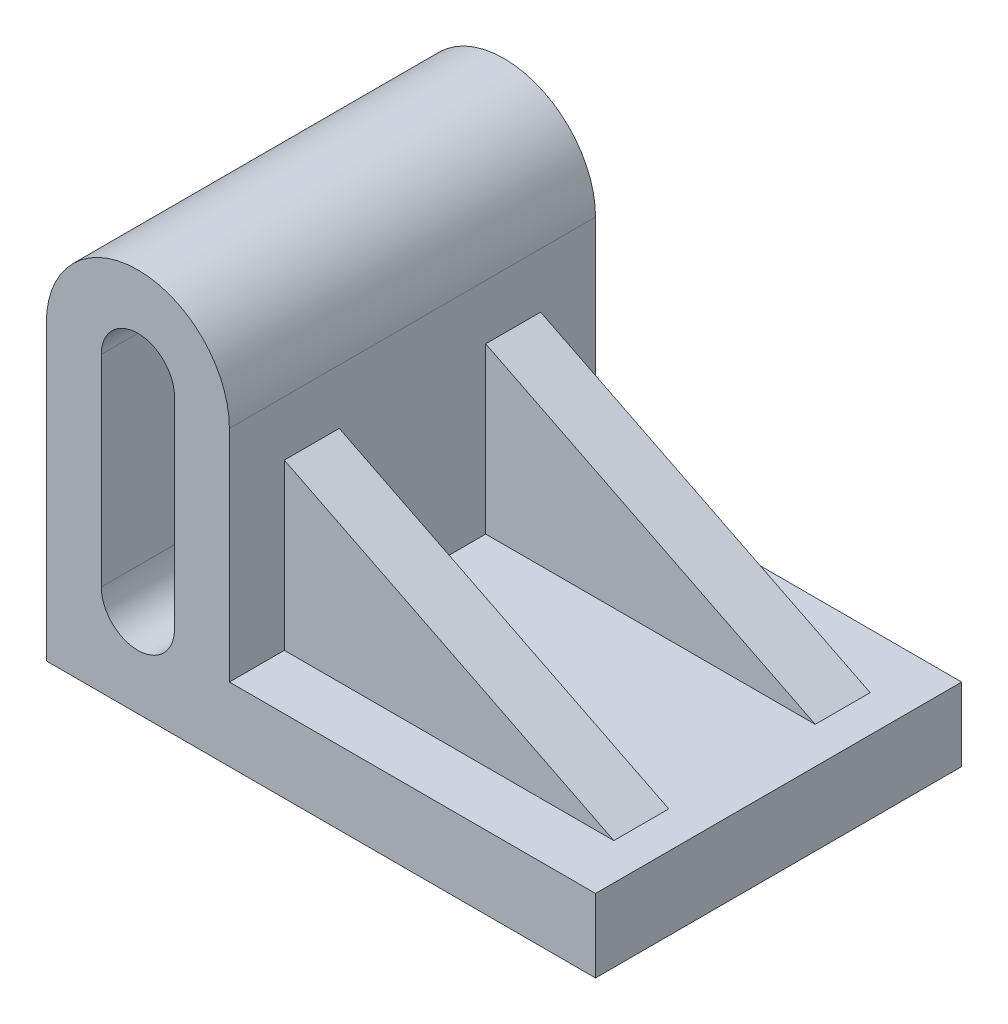
SolidWorks part; units mm, degrees
ref_plane "Front Plane" through (0, 0, 0) normal (0, 0, 1) x (1, 0, 0)
ref_plane "Top Plane" through (0, 0, 0) normal (0, 1, 0) x (1, 0, 0)
ref_plane "Right Plane" through (0, 0, 0) normal (1, 0, 0) x (0, 0, -1)
sketch "Sketch1" plane through (0, 0, 0) normal (0, 0, 1) x (1, 0, 0)
  line L0 (0, 0) -> (0, 80)
  line L1 (50, 80) -> (50, 20)
  line L2 (50, 20) -> (150, 20)
  line L3 (150, 20) -> (150, 0)
  line L4 (150, 0) -> (0, 0)
  line L5 (50, 65) -> (140, 20)
  line L6 (25, 80) -> (25, 25) construction
  line L7 (35, 80) -> (35, 25)
  line L8 (15, 80) -> (15, 25)
  arc A0 (0, 80) -> (50, 80) centre (25, 80) cw
  arc A1 (35, 80) -> (15, 80) centre (25, 80) ccw
  arc A2 (15, 25) -> (35, 25) centre (25, 25) ccw
  point P10 (25, 52.5)
  dimension "D1" = 10
  dimension "D2" = 25
  dimension "D3" = 55
  dimension "D4" = 25
  dimension "D5" = 150
  dimension "D6" = 20
  dimension "D7" = 45
  dimension "D8" = 10
extrude "Boss-Extrude1" add sketch "Sketch1" along normal mid plane 100 contours A0 L0 L4 L3 L2 L1 A2 L8 A1 L7 region at (1.831, 40, 0)
extrude "Boss-Extrude2" add sketch "Sketch1<3>" along normal blind 15 from offset 20 contours L5 L1 L2 region at (80, 35, 0)
sketch "Sketch1<3>" plane through (0, 0, 0) normal (0, 0, 1) x (1, 0, 0) same geometry as "Sketch1"
mirror "Mirror1" about plane through (0, 0, 0) normal (0, 0, 1) of "Boss-Extrude2"
